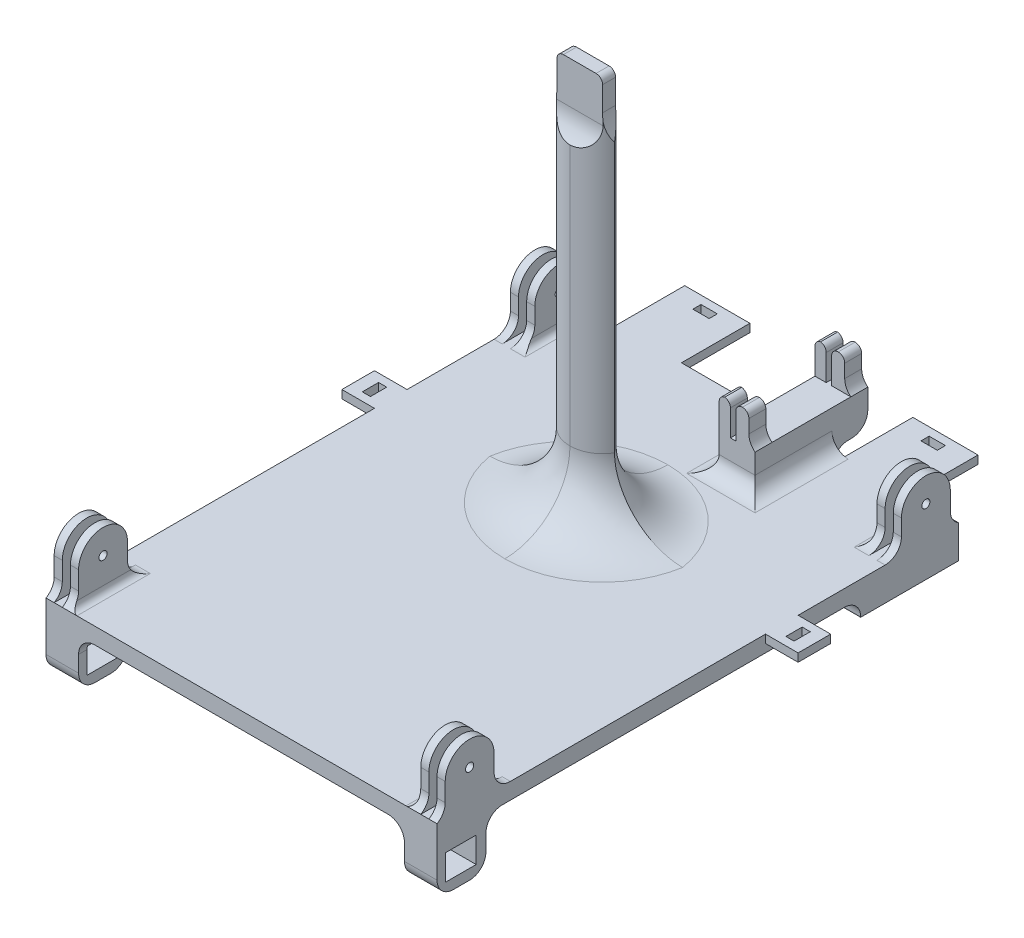
SolidWorks part; units mm, degrees
material "ABS"
ref_plane "Front Plane" through (0, 0, 0) normal (0, 0, 1) x (1, 0, 0)
ref_plane "Top Plane" through (0, 0, 0) normal (0, 1, 0) x (1, 0, 0)
ref_plane "Right Plane" through (0, 0, 0) normal (1, 0, 0) x (0, 0, -1)
sketch "Sketch1" plane through (0, 0, 0) normal (0, 1, 0) x (1, 0, 0)
  line L1 (0, 0) -> (152.4, 0)
  line L2 (0, 0) -> (0, -203.2)
  line L3 (0, -203.2) -> (152.4, -203.2)
  line L4 (152.4, 0) -> (152.4, -203.2)
  dimension "D1" = 152.4
  dimension "D2" = 203.2
extrude "Boss-Extrude1" add sketch "Sketch1" along normal blind 6.35
sketch "Sketch2" plane through (152.4, 0, 0) normal (1, 0, 0) x (0, 0, -1)
  line L1 (-203.2, 6.35) -> (-177.8, 6.35)
  line L2 (-203.2, 6.35) -> (-203.2, 31.75)
  line L3 (-203.2, 31.75) -> (-177.8, 31.75)
  line L4 (-177.8, 6.35) -> (-177.8, 31.75)
  circle A0 centre (-190.5, 19.05) radius 1.5875
  dimension "D3" = 3.175
  dimension "D1" = 25.4
  dimension "D2" = 25.4
  dimension "D4" = 12.7
  dimension "D5" = 12.7
extrude "Boss-Extrude2" add sketch "Sketch2" against normal blind 3.175
ref_plane "Plane1" through (76.2, 0, 0) normal (1, 0, 0) x (0, 0, -1)
mirror "Mirror2" about plane through (76.2, 0, 0) normal (1, 0, 0) of "Boss-Extrude2"
ref_plane "Plane2" through (0, 0, 101.6) normal (0, 0, 1) x (1, 0, 0)
mirror "Mirror3" about plane through (0, 0, 101.6) normal (0, 0, 1) of "Mirror2", "Boss-Extrude2"
ref_plane "Plane3" through (146.05, 0, 0) normal (-1, 0, 0) x (0, 0, 1)
sketch "Sketch4" plane through (146.05, 0, 0) normal (-1, 0, 0) x (0, 0, 1)
  line L4 (203.2, 6.35) -> (203.2, 31.75)
  line L5 (203.2, 31.75) -> (177.8, 31.75)
  line L6 (177.8, 31.75) -> (177.8, 6.35)
  line L7 (177.8, 6.35) -> (203.2, 6.35)
  line L8 (203.2, 6.35) -> (203.2, 31.75)
  line L9 (203.2, 31.75) -> (177.8, 31.75)
  line L10 (177.8, 31.75) -> (177.8, 6.35)
  line L11 (177.8, 6.35) -> (203.2, 6.35)
  circle A0 centre (190.5, 19.05) radius 1.5875 construction
  circle A1 centre (190.5, 19.05) radius 1.5875
  dimension "D1" = 0
extrude "Boss-Extrude3" add sketch "Sketch4" along normal blind 3.175
mirror "Mirror4" about plane through (76.2, 0, 0) normal (1, 0, 0) of "Boss-Extrude3"
mirror "Mirror5" about plane through (0, 0, 101.6) normal (0, 0, 1) of "Boss-Extrude3", "Mirror4"
sketch "Sketch5" plane through (0, 0, 0) normal (-1, 0, 0) x (0, 0, 1)
  line L0 (177.8, 6.35) -> (203.2, 6.35) construction
  line L1 (203.2, 31.75) -> (203.2, 0) construction
  line L2 (180.975, 19.05) -> (180.975, 6.35)
  line L3 (180.975, 6.35) -> (177.8, 6.35)
  line L4 (177.8, 6.35) -> (177.8, 31.75)
  line L5 (177.8, 31.75) -> (203.2, 31.75)
  line L6 (203.2, 31.75) -> (203.2, 6.35)
  line L7 (203.2, 6.35) -> (200.025, 6.35)
  line L8 (200.025, 6.35) -> (200.025, 19.05)
  arc A0 (200.025, 19.05) -> (180.975, 19.05) centre (190.5, 19.05) ccw
  dimension "D1" = 19.05
extrude "Cut-Extrude1" cut sketch "Sketch5" against normal through all
mirror "Mirror6" about plane through (0, 0, 101.6) normal (0, 0, 1) of "Cut-Extrude1"
fillet "Fillet2" radius 6.35 16 edges at (1.5875, 6.35, 200.025) (7.9375, 6.35, 200.025) (7.9375, 6.35, 180.975) (1.5875, 6.35, 180.975) (144.4625, 6.35, 180.975) (150.8125, 6.35, 180.975) (144.4625, 6.35, 200.025) (150.8125, 6.35, 200.025) (150.8125, 6.35, 22.225) (144.4625, 6.35, 22.225) (150.8125, 6.35, 3.175) (144.4625, 6.35, 3.175) (7.9375, 6.35, 3.175) (1.5875, 6.35, 3.175) (1.5875, 6.35, 22.225) (7.9375, 6.35, 22.225)
sketch "Sketch7" plane through (0, 0, 0) normal (-1, 0, 0) x (0, 0, 1)
  line L1 (203.2, 0) -> (184.15, 0)
  line L2 (203.2, 0) -> (203.2, -19.05)
  line L3 (203.2, -19.05) -> (184.15, -19.05)
  line L4 (184.15, 0) -> (184.15, -19.05)
  line L5 (187.96, -5.08) -> (199.898, -5.08)
  line L6 (187.96, -5.08) -> (187.96, -15.0368)
  line L7 (187.96, -15.0368) -> (199.898, -15.0368)
  line L8 (199.898, -5.08) -> (199.898, -15.0368)
  dimension "D1" = 19.05
  dimension "D2" = 19.05
  dimension "D3" = 9.9568
  dimension "D4" = 11.938
  dimension "D5" = 3.81
  dimension "D6" = 5.08
extrude "Boss-Extrude5" add sketch "Sketch7" against normal blind 12.7
mirror "Mirror7" about plane through (76.2, 0, 0) normal (1, 0, 0) of "Boss-Extrude5"
fillet "Fillet3" radius 6.35 4 edges at (146.05, -19.05, 203.2) (146.05, -19.05, 184.15) (6.35, -19.05, 184.15) (6.35, -19.05, 203.2)
fillet "Fillet4" radius 6.35 2 edges at (139.7, 0, 193.675) (12.7, 0, 193.675)
sketch "Sketch9" plane through (0, 6.35, 0) normal (0, 1, 0) x (1, 0, 0)
  line L0 (142.875, 0) -> (95.4786, 0) construction
  line L1 (142.875, 0) -> (9.525, 0) construction
  line L3 (103.0986, 13.97) -> (89.1286, 13.97)
  line L4 (103.0986, 13.97) -> (103.0986, -29.972)
  line L5 (103.0986, -29.972) -> (89.1286, -29.972)
  line L6 (89.1286, 13.97) -> (89.1286, -29.972)
  point P9 (101.1973, 16.1932)
  dimension "D1" = 47.3964
  dimension "D2" = 13.97
  dimension "D3" = 6.35
  dimension "D4" = 13.97
  dimension "D5" = 29.972
extrude "Boss-Extrude6" add sketch "Sketch9" along normal blind 14.1407
sketch "Sketch10" plane through (0, 20.4907, 0) normal (0, 1, 0) x (1, 0, 0)
  line L0 (89.1286, -29.972) -> (103.0986, -29.972) construction
  line L1 (95.631, -29.972) -> (93.4974, -29.972)
  line L2 (95.631, -29.972) -> (95.631, 13.97) construction
  line L3 (95.631, 13.97) -> (93.4974, 13.97)
  line L4 (93.4974, -29.972) -> (93.4974, 13.97) construction
  line L5 (103.0986, 13.97) -> (89.1286, 13.97) construction
  line L6 (89.1286, 13.97) -> (89.1286, -29.972) construction
  line L8 (93.4974, 7.366) -> (89.1286, 7.366)
  line L9 (93.4974, 7.366) -> (93.4974, 13.97)
  line L10 (93.4974, 13.97) -> (89.1286, 13.97)
  line L11 (89.1286, 7.366) -> (89.1286, 13.97)
  line L12 (93.4974, -29.972) -> (89.1286, -29.972)
  line L13 (93.4974, -29.972) -> (93.4974, -23.368)
  line L14 (93.4974, -23.368) -> (89.1286, -23.368)
  line L15 (89.1286, -29.972) -> (89.1286, -23.368)
  line L16 (95.631, -29.972) -> (100.711, -29.972)
  line L17 (95.631, -29.972) -> (95.631, -23.368)
  line L18 (95.631, -23.368) -> (100.711, -23.368)
  line L19 (100.711, -29.972) -> (100.711, -23.368)
  line L20 (95.631, 7.366) -> (100.711, 7.366)
  line L21 (95.631, 7.366) -> (95.631, 13.97)
  line L22 (95.631, 13.97) -> (100.711, 13.97)
  line L23 (100.711, 7.366) -> (100.711, 13.97)
  line M6 (103.0986, 13.97) -> (89.1286, 13.97)
  line M7 (89.1286, 13.97) -> (89.1286, -29.972)
  line M8 (89.1286, -29.972) -> (103.0986, -29.972)
  dimension "D1" = 4.3688
  dimension "D2" = 2.1336
  dimension "D3" = 6.604
  dimension "D4" = 6.604
  dimension "D5" = 6.604
  dimension "D6" = 5.08
  dimension "D7" = 5.08
  dimension "D8" = 6.604
extrude "Boss-Extrude7" add sketch "Sketch10" along normal blind 12.7 contours L19 L18 L17 M8 | L13 L14 M7 M8 | L20 L23 L21 M6 | L8 L9 M6 M7 region at (98.171, 20.4907, -10.668) region at (91.313, 20.4907, -10.668) region at (91.313, 20.4907, 26.67) region at (98.171, 20.4907, 26.67)
fillet "Fillet5" radius 6.35 1 edges at (96.1136, 6.35, 0)
fillet "Fillet6" radius 6.35 1 edges at (96.1136, 6.35, -13.97)
fillet "Fillet7" radius 6.35 2 edges at (100.711, 20.4907, 26.67) (100.711, 20.4907, -10.668)
fillet "Fillet8" radius 2.54 8 edges at (95.631, 33.1907, -10.668) (100.711, 33.1907, -10.668) (89.1286, 33.1907, 26.67) (93.4974, 33.1907, 26.67) (95.631, 33.1907, 26.67) (100.711, 33.1907, 26.67) (89.1286, 33.1907, -10.668) (93.4974, 33.1907, -10.668)
fillet "Fillet9" radius 6.35 2 edges at (89.1286, 6.35, 14.986) (103.0986, 6.35, 14.986)
fillet "Fillet10" radius 6.35 1 edges at (96.1136, 6.35, 29.972)
sketch "Sketch11" plane through (0, 0, 0) normal (0, -1, 0) x (1, 0, 0)
  line L1 (152.4, 0) -> (114.3, 0)
  line L2 (152.4, 0) -> (152.4, 38.1)
  line L3 (152.4, 38.1) -> (114.3, 38.1)
  line L4 (114.3, 0) -> (114.3, 38.1)
  dimension "D1" = 38.1
  dimension "D2" = 38.1
extrude "Boss-Extrude8" add sketch "Sketch11" along normal blind 6.5278
mirror "Mirror8" about plane through (76.2, 0, 0) normal (1, 0, 0) of "Boss-Extrude8"
fillet "Fillet11" radius 6.35 2 edges at (9.525, 0, 184.15) (142.875, 0, 184.15)
fillet "Fillet12" radius 6.35 4 edges at (38.1, 0, 19.05) (19.05, 0, 38.1) (133.35, 0, 38.1) (114.3, 0, 19.05)
fillet "Fillet13" radius 2.54 4 edges at (142.875, 6.35, 14.2875) (9.525, 6.35, 14.2875) (9.525, 6.35, 188.9125) (142.875, 6.35, 188.9125)
sketch "Sketch12" plane through (0, 6.35, 0) normal (0, 1, 0) x (1, 0, 0)
  line L0 (0, 0) -> (152.4, 0) construction
  line L1 (76.2, 0) -> (76.2, -82.8091) construction
  line L3 (63.5, -75.1891) -> (88.9, -75.1891)
  line L4 (63.5, -75.1891) -> (63.5, -62.4891)
  line L5 (63.5, -62.4891) -> (88.9, -62.4891)
  line L6 (88.9, -75.1891) -> (88.9, -62.4891)
  line L7 (63.5, -75.1891) -> (88.9, -62.4891) construction
  line L8 (63.5, -62.4891) -> (88.9, -75.1891) construction
  point P6 (76.2, -68.8391)
  point P11 (0, 0)
  point P12 (0, 0)
  dimension "D1" = 82.8091
  dimension "D2" = 7.62
  dimension "D3" = 12.7
  dimension "D4" = 25.4
extrude "Boss-Extrude9" add sketch "Sketch12" along normal blind 127
sketch "Sketch13" plane through (0, 133.35, 0) normal (0, 1, 0) x (1, 0, 0)
  line L8 (85.09, -71.3791) -> (85.09, -66.2991)
  line L9 (85.09, -66.2991) -> (67.31, -66.2991)
  line L10 (67.31, -66.2991) -> (67.31, -71.3791)
  line L11 (67.31, -71.3791) -> (85.09, -71.3791)
  line L12 (85.09, -71.3791) -> (85.09, -66.2991)
  line L13 (85.09, -66.2991) -> (67.31, -66.2991)
  line L14 (67.31, -66.2991) -> (67.31, -71.3791)
  line L15 (67.31, -71.3791) -> (85.09, -71.3791)
  dimension "D1" = 3.81
extrude "Boss-Extrude10" add sketch "Sketch13" along normal blind 25.4
fillet "Fillet14" radius 25.4 2 edges at (67.31, 133.35, 68.8391) (85.09, 133.35, 68.8391)
fillet "Fillet15" radius 12.7 2 edges at (76.2, 133.35, 66.2991) (76.2, 133.35, 71.3791)
fillet "Fillet16" radius 12.7 4 edges at (63.5, 69.85, 62.4891) (63.5, 69.85, 75.1891) (88.9, 69.85, 75.1891) (88.9, 69.85, 62.4891)
fillet "Fillet17" radius 2.54 2 edges at (67.31, 158.75, 68.8391) (85.09, 158.75, 68.8391)
fillet "Fillet18" radius 25.4 4 edges at (69.85, 6.35, 73.4876) (69.85, 6.35, 64.1906) (82.55, 6.35, 73.4876) (82.55, 6.35, 64.1906)
sketch "Sketch14" plane through (0, 6.35, 0) normal (0, 1, 0) x (1, 0, 0)
  line L0 (82.7786, 0) -> (12.065, 0) construction
  line L1 (44.45, 0) -> (19.05, 0)
  line L2 (44.45, 0) -> (44.45, 26.67)
  line L3 (44.45, 26.67) -> (19.05, 26.67)
  line L4 (19.05, 0) -> (19.05, 26.67)
  line L5 (103.0986, 13.97) -> (89.1286, 13.97) construction
  dimension "D1" = 12.7
  dimension "D2" = 25.4
  dimension "D3" = 19.05
extrude "Boss-Extrude11" add sketch "Sketch14" against normal blind 3.175
mirror "Mirror9" about plane through (76.2, 0, 0) normal (1, 0, 0) of "Boss-Extrude11"
sketch "Sketch15" plane through (0, 6.35, 0) normal (0, 1, 0) x (1, 0, 0)
  line L0 (44.45, 26.67) -> (19.05, 26.67) construction
  line L1 (34.925, 20.32) -> (28.575, 20.32)
  line L2 (34.925, 20.32) -> (34.925, 23.495)
  line L3 (34.925, 23.495) -> (28.575, 23.495)
  line L4 (28.575, 20.32) -> (28.575, 23.495)
  line L7 (19.05, 26.67) -> (19.05, 0) construction
  point P6 (31.75, 20.32)
  dimension "D1" = 3.175
  dimension "D2" = 3.175
  dimension "D3" = 6.35
  dimension "D4" = 12.7
extrude "Cut-Extrude3" cut sketch "Sketch15" against normal through all
mirror "Mirror10" about plane through (76.2, 0, 0) normal (1, 0, 0) of "Cut-Extrude3"
ref_plane "Plane4" through (8.763, 0, 0) normal (1, 0, 0) x (0, 0, -1)
sketch "Sketch16" plane through (0, 6.35, 0) normal (0, 1, 0) x (1, 0, 0)
  line L0 (38.6329, -68.8391) -> (0, -68.8391) construction
  line L1 (0, -28.575) -> (0, -174.625) construction
  line L2 (-12.7, -68.8391) -> (0, -68.8391) construction
  line L3 (0, -62.4891) -> (-12.7, -62.4891)
  line L4 (0, -62.4891) -> (0, -75.1891)
  line L5 (0, -75.1891) -> (-12.7, -75.1891)
  line L6 (-12.7, -62.4891) -> (-12.7, -75.1891)
  line L8 (-4.7625, -65.6641) -> (-7.9375, -65.6641)
  line L9 (-4.7625, -65.6641) -> (-4.7625, -72.0141)
  line L10 (-4.7625, -72.0141) -> (-7.9375, -72.0141)
  line L11 (-7.9375, -65.6641) -> (-7.9375, -72.0141)
  line L12 (-4.7625, -65.6641) -> (-7.9375, -72.0141) construction
  line L13 (-4.7625, -72.0141) -> (-7.9375, -65.6641) construction
  point P1 (-6.35, -68.8391)
  dimension "D1" = 12.7
  dimension "D2" = 12.7
  dimension "D3" = 6.35
  dimension "D4" = 3.175
extrude "Boss-Extrude12" add sketch "Sketch16" against normal blind 3.175
mirror "Mirror11" about plane through (76.2, 0, 0) normal (1, 0, 0) of "Boss-Extrude12"
